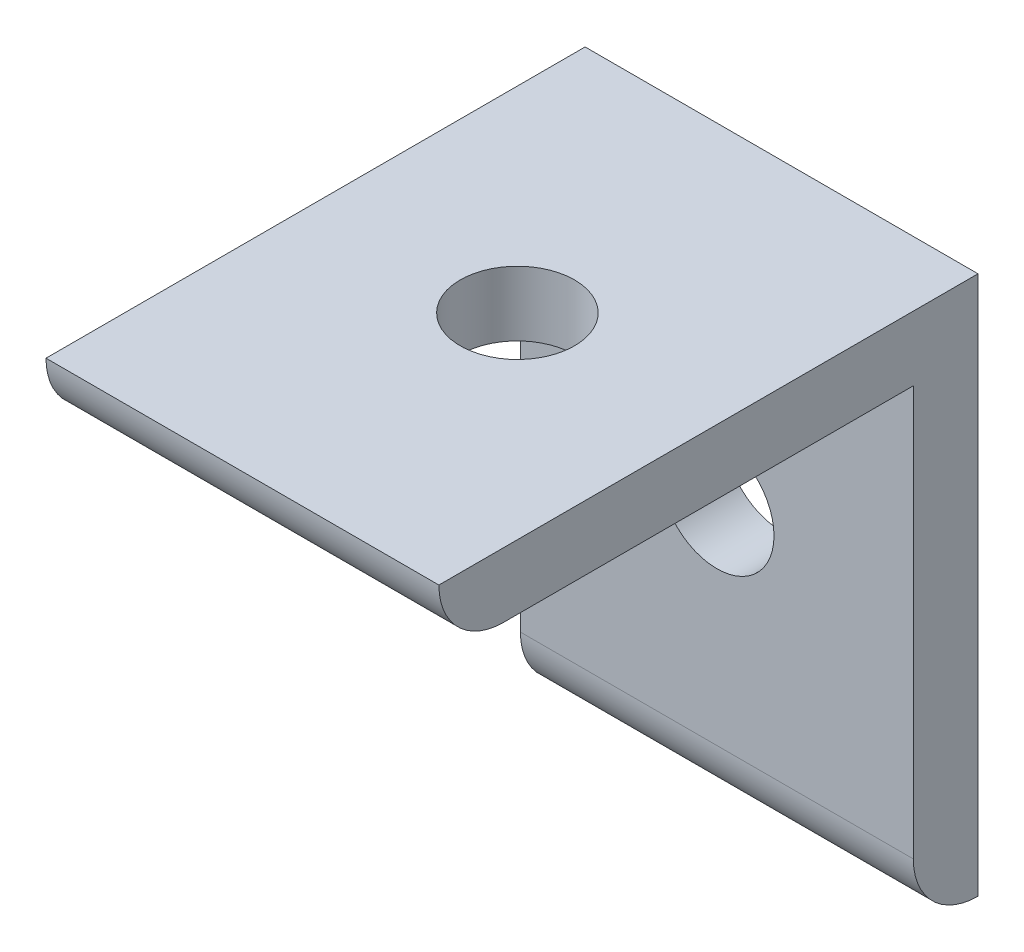
SolidWorks part; units mm, degrees
ref_plane "Plano frontal" through (0, 0, 0) normal (0, 0, 1) x (1, 0, 0)
ref_plane "Plano superior" through (0, 0, 0) normal (0, 1, 0) x (1, 0, 0)
ref_plane "Plano direito" through (0, 0, 0) normal (1, 0, 0) x (0, 0, -1)
sketch "Esboço1" plane through (0, 0, 0) normal (0, 0, 1) x (1, 0, 0)
  line L1 (-88.5809, -309.6657) -> (-70.3609, -309.6657)
  line L2 (-88.5809, -309.6657) -> (-88.5809, -334.6657)
  line L3 (-88.5809, -334.6657) -> (-70.3609, -334.6657)
  line L4 (-70.3609, -309.6657) -> (-70.3609, -334.6657)
  dimension "D1" = 25
  dimension "D2" = 18.22
extrude "Ressalto-extrusão1" add sketch "Esboço1" along normal blind 3
sketch "Esboço2" plane through (0, 0, 3) normal (0, 0, 1) x (1, 0, 0)
  line L0 (-70.3609, -334.6657) -> (-70.3609, -309.6657) construction
  line L1 (-88.5809, -309.6657) -> (-70.3609, -309.6657)
  line L2 (-88.5809, -309.6657) -> (-88.5809, -312.6657)
  line L3 (-88.5809, -312.6657) -> (-70.3609, -312.6657)
  line L4 (-70.3609, -309.6657) -> (-70.3609, -312.6657)
  dimension "D1" = 3
extrude "Ressalto-extrusão2" add sketch "Esboço2" along normal blind 22
sketch "Esboço3" plane through (0, 0, 3) normal (0, 0, 1) x (1, 0, 0)
  line L0 (-70.3609, -309.6657) -> (-88.5809, -309.6657) construction
  line L1 (-88.5809, -312.6657) -> (-88.5809, -334.6657) construction
  circle A0 centre (-79.4709, -321.9157) radius 2.65
  dimension "D1" = 12.25
  dimension "D2" = 9.11
extrude "Corte-extrusão1" cut sketch "Esboço3" against normal blind 25
sketch "Esboço4" plane through (0, -312.6657, 0) normal (0, -1, 0) x (1, 0, 0)
  line L0 (-70.3609, 0) -> (-88.5809, 0) construction
  line L1 (-88.5809, 25) -> (-88.5809, 3) construction
  circle A0 centre (-79.4709, 12.25) radius 2.65
  dimension "D1" = 5.3
  dimension "D2" = 12.25
  dimension "D3" = 9.11
extrude "Corte-extrusão2" cut sketch "Esboço4" against normal blind 25
fillet "Filete1" radius 3 2 edges at (-79.4709, -312.6657, 25) (-79.4709, -334.6657, 3)
